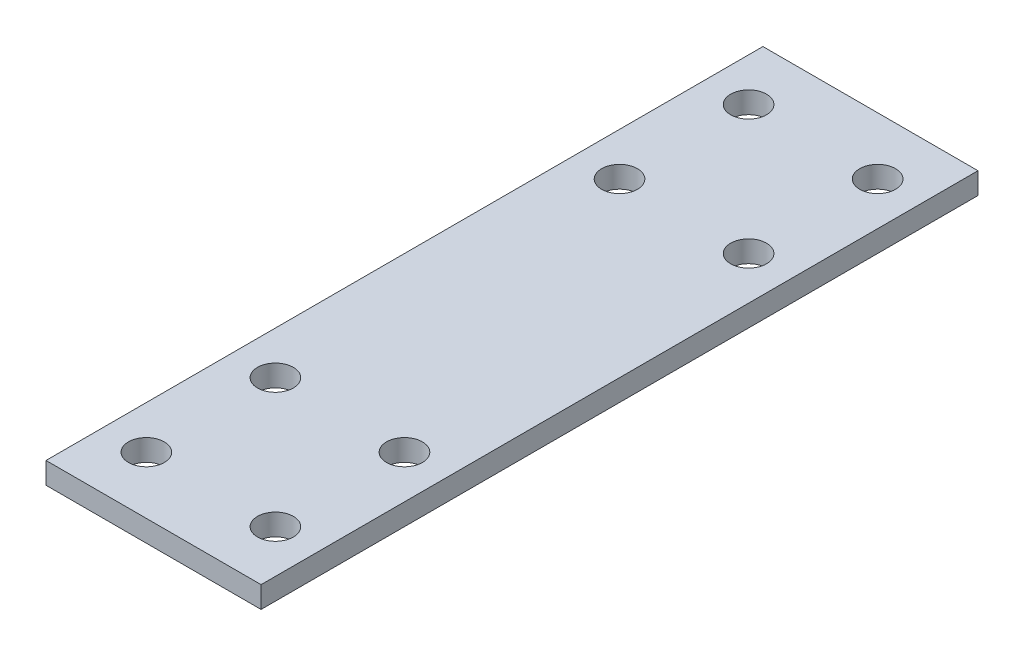
SolidWorks part; units mm, degrees
ref_plane "Front Plane" through (0, 0, 0) normal (0, 0, 1) x (1, 0, 0)
ref_plane "Top Plane" through (0, 0, 0) normal (0, 1, 0) x (1, 0, 0)
ref_plane "Right Plane" through (0, 0, 0) normal (1, 0, 0) x (0, 0, -1)
sketch "Sketch1" plane through (0, 0, 0) normal (0, 1, 0) x (1, 0, 0)
  line L1 (-22.3792, 49.995) -> (7.6208, 49.995)
  line L2 (-22.3792, 49.995) -> (-22.3792, -50.005)
  line L3 (-22.3792, -50.005) -> (7.6208, -50.005)
  line L4 (7.6208, 49.995) -> (7.6208, -50.005)
  circle A0 centre (-16.3792, -24.005) radius 2.5
  circle A1 centre (1.6208, -24.005) radius 2.5
  circle A2 centre (1.6208, -42.005) radius 2.5
  circle A3 centre (-16.3792, -42.005) radius 2.5
  circle A4 centre (-16.3792, 41.995) radius 2.5
  circle A5 centre (-16.3792, 23.995) radius 2.5
  circle A6 centre (1.6208, 41.995) radius 2.5
  circle A7 centre (1.6208, 23.995) radius 2.5
  dimension "D3" = 5
  dimension "D4" = 5
  dimension "D5" = 5
  dimension "D6" = 5
  dimension "D12" = 5
  dimension "D13" = 5
  dimension "D14" = 5
  dimension "D15" = 5
  dimension "D18" = 18
  dimension "D1" = 30
  dimension "D2" = 100
  dimension "D7" = 18
  dimension "D8" = 18
  dimension "D9" = 18
  dimension "D10" = 8
  dimension "D11" = 6
  dimension "D16" = 18
  dimension "D17" = 18
  dimension "D19" = 8
  dimension "D20" = 6
  dimension "D30" = 0
extrude "Boss-Extrude1" add sketch "Sketch1" along normal blind 3
